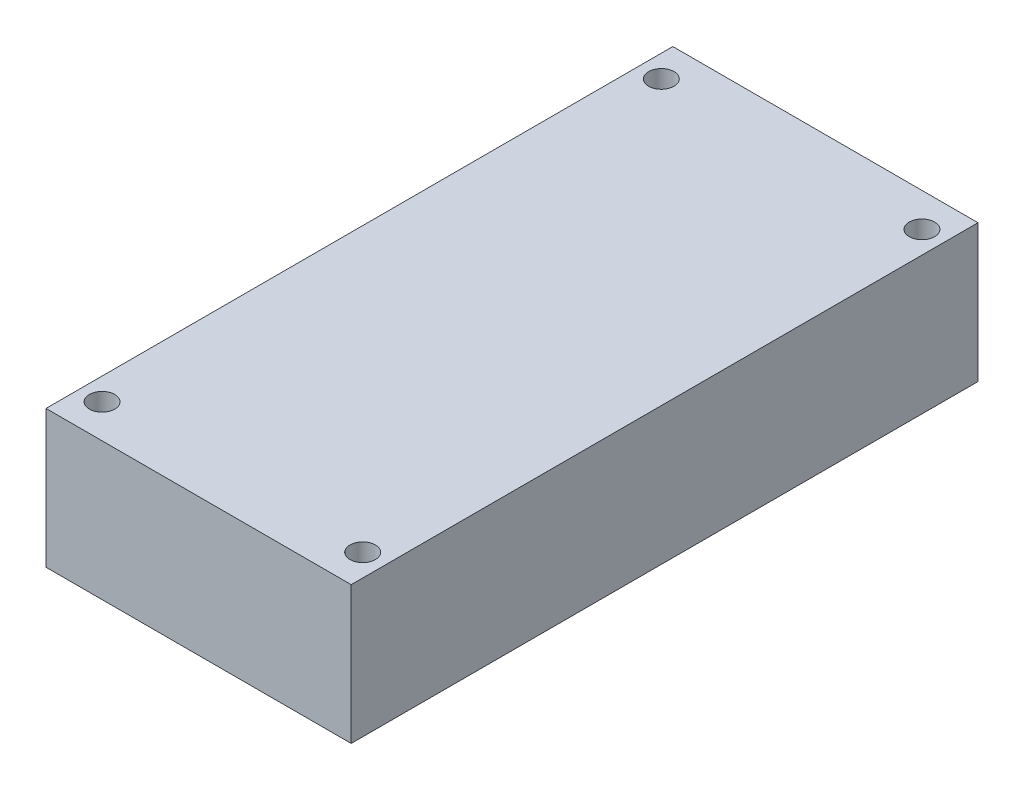
SolidWorks part; units mm, degrees
ref_plane "Front Plane" through (0, 0, 0) normal (0, 0, 1) x (1, 0, 0)
ref_plane "Top Plane" through (0, 0, 0) normal (0, 1, 0) x (1, 0, 0)
ref_plane "Right Plane" through (0, 0, 0) normal (1, 0, 0) x (0, 0, -1)
sketch "Sketch1" plane through (0, 0, 0) normal (0, 1, 0) x (1, 0, 0)
  line L0 (3.105, 82.605) -> (0, 87.31) construction
  line L1 (0, 0) -> (42.51, 0)
  line L2 (0, 0) -> (0, 87.31)
  line L3 (0, 87.31) -> (42.51, 87.31)
  line L4 (42.51, 0) -> (42.51, 87.31)
  line L5 (3.105, 82.605) -> (39.405, 82.605) construction
  line L6 (3.105, 82.605) -> (3.105, 4.705) construction
  line L7 (3.105, 4.705) -> (39.405, 4.705) construction
  line L8 (39.405, 82.605) -> (39.405, 4.705) construction
  line L9 (39.405, 82.605) -> (42.51, 87.31) construction
  line L10 (39.405, 4.705) -> (42.51, 0) construction
  line L11 (3.105, 4.705) -> (0, 0) construction
  circle A0 centre (3.105, 82.605) radius 1.77
  circle A1 centre (39.405, 82.605) radius 1.77
  circle A2 centre (3.105, 4.705) radius 1.77
  circle A3 centre (39.405, 4.705) radius 1.77
  dimension "D2" = 3.54
  dimension "D1" = 87.31
  dimension "42.51" = 42.51
  dimension "D3" = 77.9
  dimension "D4" = 36.3
extrude "Boss-Extrude1" add sketch "Sketch1" along normal blind 19.16
